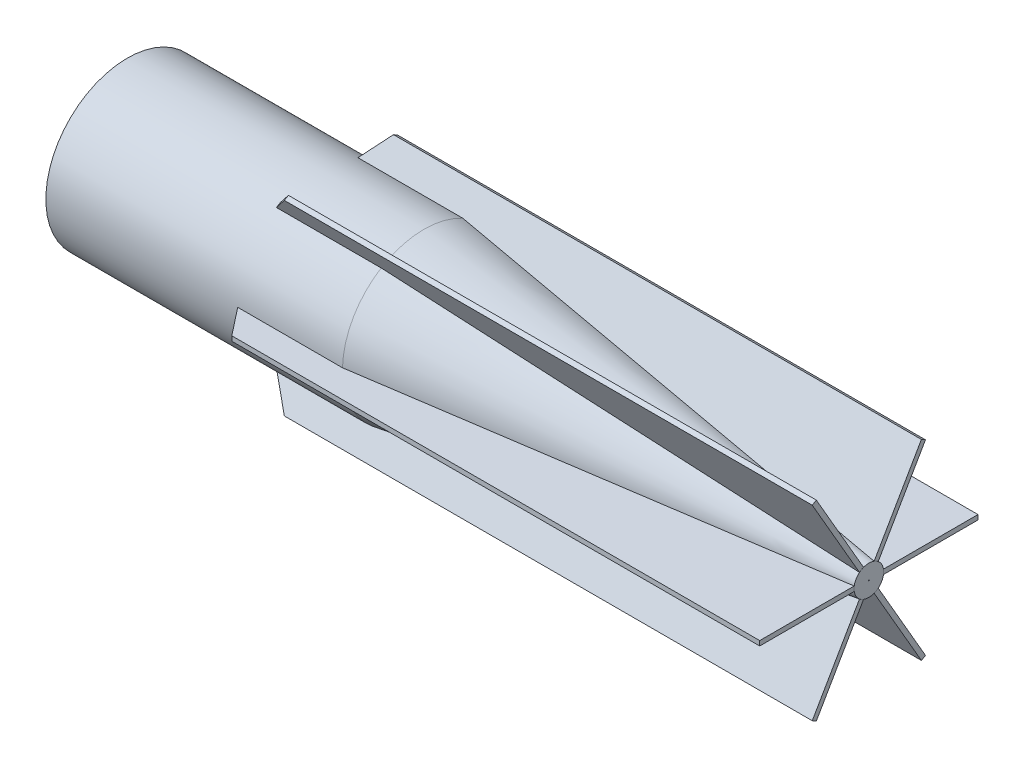
SolidWorks part; units mm, degrees
ref_plane "Front Plane" through (0, 0, 0) normal (0, 0, 1) x (1, 0, 0)
ref_plane "Top Plane" through (0, 0, 0) normal (0, 1, 0) x (1, 0, 0)
ref_plane "Right Plane" through (0, 0, 0) normal (1, 0, 0) x (0, 0, -1)
sketch "Sketch1" plane through (0, 0, 0) normal (0, 1, 0) x (1, 0, 0)
  line L0 (0, -22.5) -> (-465.3643, -22.5)
  line L1 (0, 0) -> (-250, 0)
  line L2 (0, 0) -> (0, 5)
  line L3 (0, 5) -> (-250, 5)
  line L4 (-250, 0) -> (-250, 5)
  line L5 (0, -22.5) -> (0, -17.5)
  line L6 (0, -17.5) -> (-150, 5)
  line L7 (-150, 0) -> (0, -22.5)
  line L8 (0, -22.35) -> (-1, -22.35)
  dimension "D1" = 250
  dimension "D2" = 5
  dimension "D3" = 22.5
  dimension "D4" = 5
  dimension "D5" = 150
  dimension "D6" = 1
revolve "Revolve1" add sketch "Sketch1" angle 360 about L0 region at (-191.2698, 0, -2.381) region at (-67.0214, 0, 10.0507)
sketch "Sketch3" plane through (0, 0, 0) normal (0, 1, 0) x (1, 0, 0)
  line L0 (-203, -17.5) -> (-178, 14.3)
  line L1 (0, -17.5) -> (-203, -17.5)
  line L2 (0, -17.5) -> (0, 14.3)
  line L3 (0, 14.3) -> (-203, 14.3)
  line L4 (-203, -17.5) -> (-203, 14.3)
  line L5 (0, -17.5) -> (-150, 5) construction
  line L6 (-150, 5) -> (-250, 5) construction
  line L7 (0, -17.5) -> (-150, 5)
  line L8 (-150, 5) -> (-250, 5)
  line L9 (-0.2967, -19.4779) -> (-150.1492, 3)
  line L10 (-150.1492, 3) -> (-250, 3)
  dimension "D1" = 203
  dimension "D2" = 178
  dimension "D3" = 31.8
  dimension "D4" = 2
extrude "Boss-Extrude2" add sketch "Sketch3" along normal mid plane 1.5875 contours L8 L7 L2 L3 L0 | L10 L9 L1 L7 L8 L0 region at (-96.218, 0, 4.6051) region at (-70.4315, 0, -3.5628)
pattern_circular "CirPattern2" count 6 over 360 about axis through (0, 0, 22.5) along (-1, 0, 0) of "Boss-Extrude2" reverse direction yes
